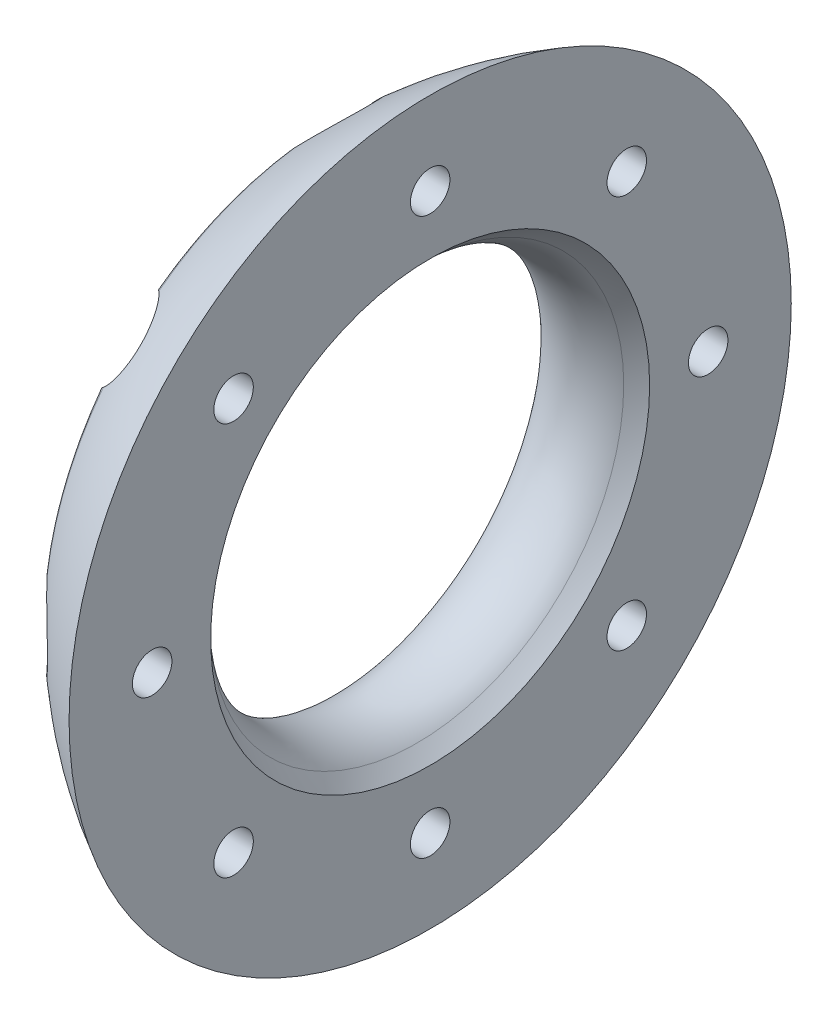
SolidWorks part; units mm, degrees
ref_plane "Vorne" through (0, 0, 0) normal (0, 0, 1) x (1, 0, 0)
ref_plane "Oben" through (0, 0, 0) normal (0, 1, 0) x (1, 0, 0)
ref_plane "Rechts" through (0, 0, 0) normal (1, 0, 0) x (0, 0, -1)
sketch "Skizze1" plane through (0, 0, 0) normal (0, 1, 0) x (1, 0, 0)
  line L0 (-13.2288, 15) -> (-13.2288, 24.6779)
  line L1 (-16.9706, 16.9706) -> (0, 0) construction
  line L2 (-55, 0) -> (55, 0) construction
  line L3 (0, 0) -> (-16.9706, 0) construction
  arc A0 (-13.2288, 15) -> (-14.1421, 14.1421) centre (0, 0) ccw
  arc A1 (-14.1421, 14.1421) -> (-19.799, 19.799) centre (-16.9706, 16.9706) cw
  arc A2 (-19.799, 19.799) -> (-13.2288, 24.6779) centre (0, 0) cw
  dimension "D2" = 20
  dimension "D4" = 28
  dimension "D1" = 45
  dimension "D3" = 15
revolve "Rotation1" add sketch "Skizze1" angle 360 about L3
sketch "Skizze2" plane through (0, 0, 0) normal (0, 0, 1) x (1, 0, 0)
  line L0 (-13.2288, 19) -> (-21.0438, 19) construction
  line L1 (-13.2288, 19) -> (-13.2288, 20.35)
  line L2 (-13.2288, -24.6779) -> (-13.2288, 24.6779) construction
  line L3 (-13.2288, 20.35) -> (-15.2288, 20.35)
  line L4 (-15.2288, 20.35) -> (-15.2288, 21.75)
  line L5 (-15.2288, 21.75) -> (-23.2288, 21.75)
  line L6 (-23.2288, 21.75) -> (-23.2288, 19)
  line L7 (-23.2288, 19) -> (-13.2288, 19)
  line L9 (4.258, 0) -> (-4.258, 0) construction
  line L10 (-23.2288, 19) -> (-23.2288, 16.25) construction
  line L11 (-23.2288, 16.25) -> (-15.2288, 16.25) construction
  line L12 (-15.2288, 16.25) -> (-15.2288, 17.65) construction
  line L13 (-15.2288, 17.65) -> (-13.2288, 17.65) construction
  dimension "D1" = 19
  dimension "D2" = 1.35
  dimension "D3" = 2.75
  dimension "D4" = 2
  dimension "D5" = 8
revolve "Schnitt-Rotation1" cut sketch "Skizze2" angle 360 about L7
ref_axis "Achse1" through (-23.7288, 0, 0) along (1, 0, 0)
pattern_circular "Kreismuster1" count 8 over 360 about axis through (-23.7288, 0, 0) along (1, 0, 0) of "Schnitt-Rotation1"
